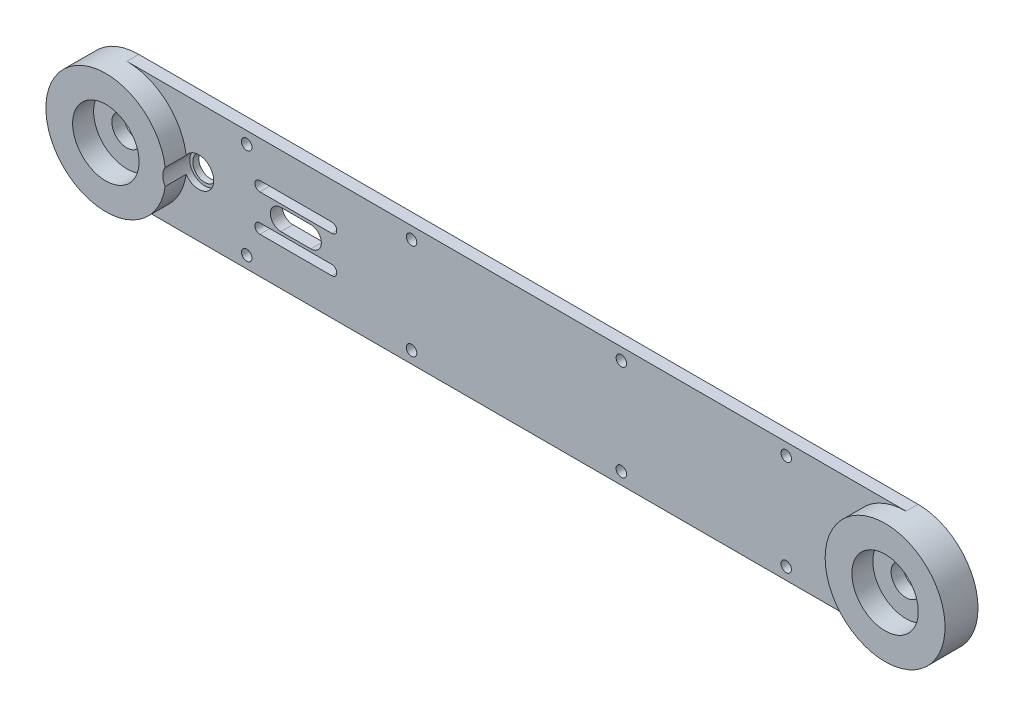
SolidWorks part; units mm, degrees
ref_plane "Ebene vorne" through (0, 0, 0) normal (0, 0, 1) x (1, 0, 0)
ref_plane "Ebene oben" through (0, 0, 0) normal (0, 1, 0) x (1, 0, 0)
ref_plane "Ebene rechts" through (0, 0, 0) normal (1, 0, 0) x (0, 0, -1)
sketch "Skizze1" plane through (0, 0, 0) normal (0, 0, 1) x (1, 0, 0)
  line L0 (-130, 0) -> (0, 0) construction
  line L1 (-130, -20) -> (130, -20)
  line L2 (-130, -20) -> (-130, 20) construction
  line L3 (-130, 20) -> (130, 20)
  line L4 (130, -20) -> (130, 20) construction
  line L5 (-130, -20) -> (130, 20) construction
  line L6 (-130, 20) -> (130, -20) construction
  line L7 (0, 0) -> (130, 0) construction
  arc A0 (-130, 20) -> (-130, -20) centre (-130, 0) ccw
  arc A1 (130, 20) -> (130, -20) centre (130, 0) cw
  point P0 (0, 0)
  dimension "D1" = 260
  dimension "D2" = 40
extrude "Aufsatz-Linear austragen1" add sketch "Skizze1" along normal blind 4
sketch "Skizze2" plane through (0, 0, 4) normal (0, 0, 1) x (1, 0, 0)
  circle A0 centre (-130, 0) radius 20
  circle A1 centre (-130, 0) radius 11.075
  dimension "D1" = 22.15
extrude "Aufsatz-Linear austragen2" add sketch "Skizze2" along normal blind 7
sketch "Skizze3" plane through (0, 0, 4) normal (0, 0, 1) x (1, 0, 0)
  circle A0 centre (-130, 0) radius 5
  dimension "D1" = 10
extrude "Schnitt-Linear austragen1" cut sketch "Skizze3" against normal through all and the other way through all
mirror "Spiegeln1" about plane through (0, 0, 0) normal (1, 0, 0) of "Aufsatz-Linear austragen2", "Schnitt-Linear austragen1"
sketch "Skizze4" plane through (0, 0, 4) normal (0, 0, 1) x (1, 0, 0)
  line L0 (-130, 20) -> (130, 20) construction
  line L1 (0, 0) -> (-130, 0) construction
  line L2 (0, 0) -> (0, 20) construction
  line L3 (-90, 12) -> (-35, 12) construction
  line L4 (-90, 14.25) -> (-35, 14.25) construction
  circle A0 centre (-130, 0) radius 30 construction
  circle A1 centre (-90, 16) radius 4 construction
  circle A2 centre (-90, 16) radius 1.75
  circle A3 centre (-90, -16) radius 4 construction
  circle A4 centre (-90, -16) radius 1.75
  circle A5 centre (90, -16) radius 4 construction
  circle A6 centre (90, 16) radius 4 construction
  circle A7 centre (90, -16) radius 1.75
  circle A8 centre (90, 16) radius 1.75
  circle A9 centre (-35, 16) radius 4 construction
  circle A10 centre (-35, 16) radius 1.75
  circle A11 centre (-35, -16) radius 4 construction
  circle A12 centre (-35, -16) radius 1.75
  circle A13 centre (35, -16) radius 4 construction
  circle A14 centre (35, 16) radius 4 construction
  circle A15 centre (35, -16) radius 1.75
  circle A16 centre (35, 16) radius 1.75
  point P29 (-45.2018, 16)
  dimension "D1" = 60
  dimension "D2" = 8
  dimension "D3" = 3.5
  dimension "D4" = 40
  dimension "D5" = 55
extrude "Schnitt-Linear austragen2" cut sketch "Skizze4" against normal through all
sketch "Skizze5" plane through (0, 0, 0) normal (0, 0, -1) x (-1, 0, 0)
  line L0 (130, 0) -> (106, 0) construction
  circle A0 centre (106, 0) radius 4
  dimension "D1" = 8
  dimension "D2" = 24
extrude "Schnitt-Linear austragen3" cut sketch "Skizze5" against normal through all
sketch "Skizze6" plane through (0, 0, 4) normal (0, 0, 1) x (1, 0, 0)
  circle A0 centre (-106, 0) radius 5
  dimension "D1" = 10
extrude "Schnitt-Linear austragen4" cut sketch "Skizze6" against normal blind 2 and the other way through all
sketch "Skizze7" plane through (0, 0, 0) normal (0, 0, -1) x (-1, 0, 0)
  line L0 (0, 0) -> (106, 0) construction
  line L1 (68.6, 0) -> (78.6, 0) construction
  line L2 (68.6, 3.5) -> (78.6, 3.5)
  line L3 (68.6, -3.5) -> (78.6, -3.5)
  line L4 (61.6, 6.12) -> (85.6, 6.12) construction
  line L5 (61.6, 7.77) -> (85.6, 7.77)
  line L6 (61.6, 4.47) -> (85.6, 4.47)
  line L7 (61.6, -6.12) -> (85.6, -6.12) construction
  line L8 (61.6, -7.77) -> (85.6, -7.77)
  line L9 (61.6, -4.47) -> (85.6, -4.47)
  arc A0 (68.6, 3.5) -> (68.6, -3.5) centre (68.6, 0) ccw
  arc A1 (78.6, -3.5) -> (78.6, 3.5) centre (78.6, 0) ccw
  arc A2 (61.6, 7.77) -> (61.6, 4.47) centre (61.6, 6.12) ccw
  arc A3 (85.6, 4.47) -> (85.6, 7.77) centre (85.6, 6.12) ccw
  arc A4 (61.6, -7.77) -> (61.6, -4.47) centre (61.6, -6.12) cw
  arc A5 (85.6, -4.47) -> (85.6, -7.77) centre (85.6, -6.12) cw
  point P6 (73.6, 0)
  point P13 (73.6, 6.12)
  point P20 (73.6, -6.12)
  point P25 (106, 0)
  dimension "D1" = 7
  dimension "D2" = 3.3
  dimension "D3" = 7
  dimension "D4" = 7
  dimension "D5" = 6.12
  dimension "D6" = 24
  dimension "D7" = 32.4
extrude "Schnitt-Linear austragen5" cut sketch "Skizze7" against normal through all
